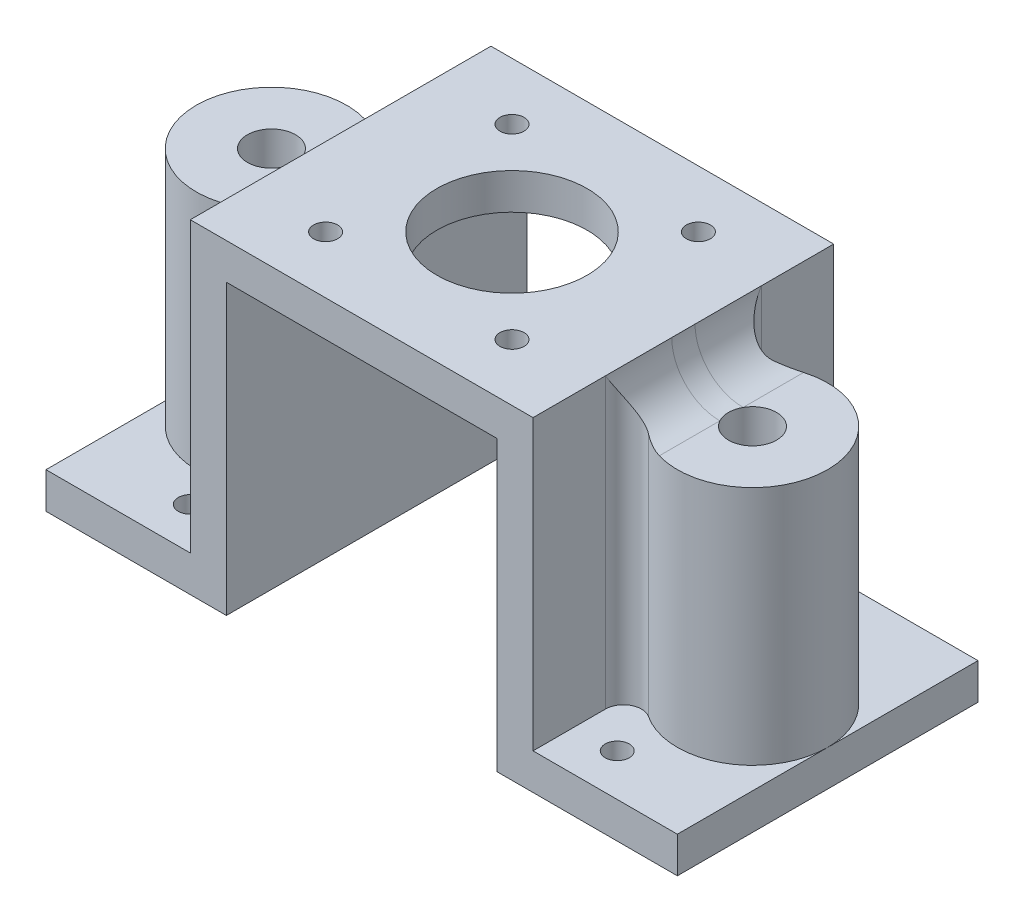
SolidWorks part; units mm, degrees
ref_plane "Plano frontal" through (0, 0, 0) normal (0, 0, 1) x (1, 0, 0)
ref_plane "Plano superior" through (0, 0, 0) normal (0, 1, 0) x (1, 0, 0)
ref_plane "Plano direito" through (0, 0, 0) normal (1, 0, 0) x (0, 0, -1)
sketch "Esboço1" plane through (0, 0, 0) normal (0, 0, 1) x (1, 0, 0)
  line L0 (-28.5, 54) -> (28.5, 54)
  line L1 (28.5, 54) -> (28.5, 6)
  line L2 (52.5, 6) -> (28.5, 6)
  line L3 (52.5, 6) -> (52.5, 0)
  line L4 (52.5, 0) -> (22.5, 0)
  line L5 (22.5, 0) -> (22.5, 48)
  line L6 (22.5, 48) -> (-22.5, 48)
  line L7 (28.5, 6) -> (22.5, 6) construction
  line L8 (22.5, 48) -> (22.5, 54) construction
  line L9 (0, 63.425) -> (0, 0) construction
  line L10 (-22.5, 48) -> (-22.5, 54) construction
  line L11 (-28.5, 6) -> (-22.5, 6) construction
  line L12 (-22.5, 0) -> (-22.5, 48)
  line L13 (-52.5, 0) -> (-22.5, 0)
  line L14 (-52.5, 6) -> (-52.5, 0)
  line L15 (-52.5, 6) -> (-28.5, 6)
  line L16 (-28.5, 54) -> (-28.5, 6)
  point P9 (0, 0)
  point P12 (0, 54)
  point P19 (0, 48)
  point P23 (0, 54)
  dimension "D1" = 48
  dimension "D2" = 6
  dimension "D3" = 45
  dimension "D4" = 105
extrude "Ressalto-extrusão1" add sketch "Esboço1" along normal mid plane 50
sketch "Esboço2" plane through (0, 54, 0) normal (0, 1, 0) x (1, 0, 0)
  line L0 (0, 25) -> (0, -25) construction
  line L1 (28.5, 25) -> (-28.5, 25) construction
  line L2 (28.5, -25) -> (-28.5, -25) construction
  line L4 (-15.5, 15.5) -> (15.5, 15.5) construction
  line L5 (-15.5, 15.5) -> (-15.5, -15.5) construction
  line L6 (-15.5, -15.5) -> (15.5, -15.5) construction
  line L7 (15.5, 15.5) -> (15.5, -15.5) construction
  line L8 (-15.5, 15.5) -> (15.5, -15.5) construction
  line L9 (-15.5, -15.5) -> (15.5, 15.5) construction
  circle A0 centre (0, 0) radius 12.5
  circle A1 centre (-15.5, 15.5) radius 2
  circle A2 centre (15.5, 15.5) radius 2
  circle A3 centre (15.5, -15.5) radius 2
  circle A4 centre (-15.5, -15.5) radius 2
  dimension "D1" = 4
  dimension "D3" = 25
  dimension "D2" = 31
extrude "Corte-extrusão1" cut sketch "Esboço2" against normal blind 42
sketch "Esboço3" plane through (0, 6, 0) normal (0, 1, 0) x (1, 0, 0)
  line L0 (27.7526, 2.5) -> (28.5, 2.5)
  line L2 (0, 35.3204) -> (0, -32.8451) construction
  line L3 (0, 0) -> (71.2121, 0) construction
  line L4 (27.7526, -2.5) -> (28.5, -2.5)
  line L6 (28.5, -2.5) -> (28.5, 2.5)
  line L7 (-27.7526, -2.5) -> (-28.5, -2.5)
  line L8 (-28.5, -2.5) -> (-28.5, 2.5)
  line L9 (-27.7526, 2.5) -> (-28.5, 2.5)
  line L10 (28.5, -25) -> (28.5, 25) construction
  arc A0 (27.7526, -2.5) -> (27.7526, 2.5) centre (40, 0) ccw
  circle A1 centre (40, 0) radius 4
  circle A2 centre (-40, 0) radius 4
  arc A3 (-27.7526, -2.5) -> (-27.7526, 2.5) centre (-40, 0) cw
  dimension "D2" = 25
  dimension "D3" = 8
  dimension "D1" = 5
  dimension "D4" = 40
extrude "Ressalto-extrusão2" add sketch "Esboço3" along normal blind 40
fillet "Filete1" radius 8 2 edges at (-28.5, 46, 0) (28.5, 46, 0)
sketch "Esboço4" plane through (0, 6, 0) normal (0, 1, 0) x (1, 0, 0)
  line L0 (-35.5, 18) -> (-35.5, 25) construction
  line L1 (-28.5, 25) -> (-52.5, 25) construction
  line L2 (-35.5, 18) -> (-52.5, 18) construction
  line L3 (-52.5, -25) -> (-52.5, 0) construction
  line L4 (-59.6325, 0) -> (0, 0) construction
  line L5 (0, 0) -> (0, 35.3341) construction
  circle A0 centre (-35.5, 18) radius 2
  circle A1 centre (-35.5, 18) radius 5.5 construction
  circle A2 centre (35.5, 18) radius 2
  circle A3 centre (35.5, -18) radius 2
  circle A4 centre (-35.5, -18) radius 2
  point P19 (-46.973, 16.973)
  point P20 (-34.1677, 17.9698)
  point P21 (-34.4035, 18.6409)
  point P22 (-35.5382, 18.1468)
  point P23 (0, 0)
  point P24 (-34.4818, 18.0248)
  dimension "D1" = 4
  dimension "D2" = 11
  dimension "D3" = 7
  dimension "D4" = 17
extrude "Corte-extrusão2" cut sketch "Esboço4" against normal through all
fillet "Filete5" radius 3 4 edges at (-28.5, 30, -4.899) (-28.5, 30, 4.899) (28.5, 30, -4.899) (28.5, 30, 4.899)
